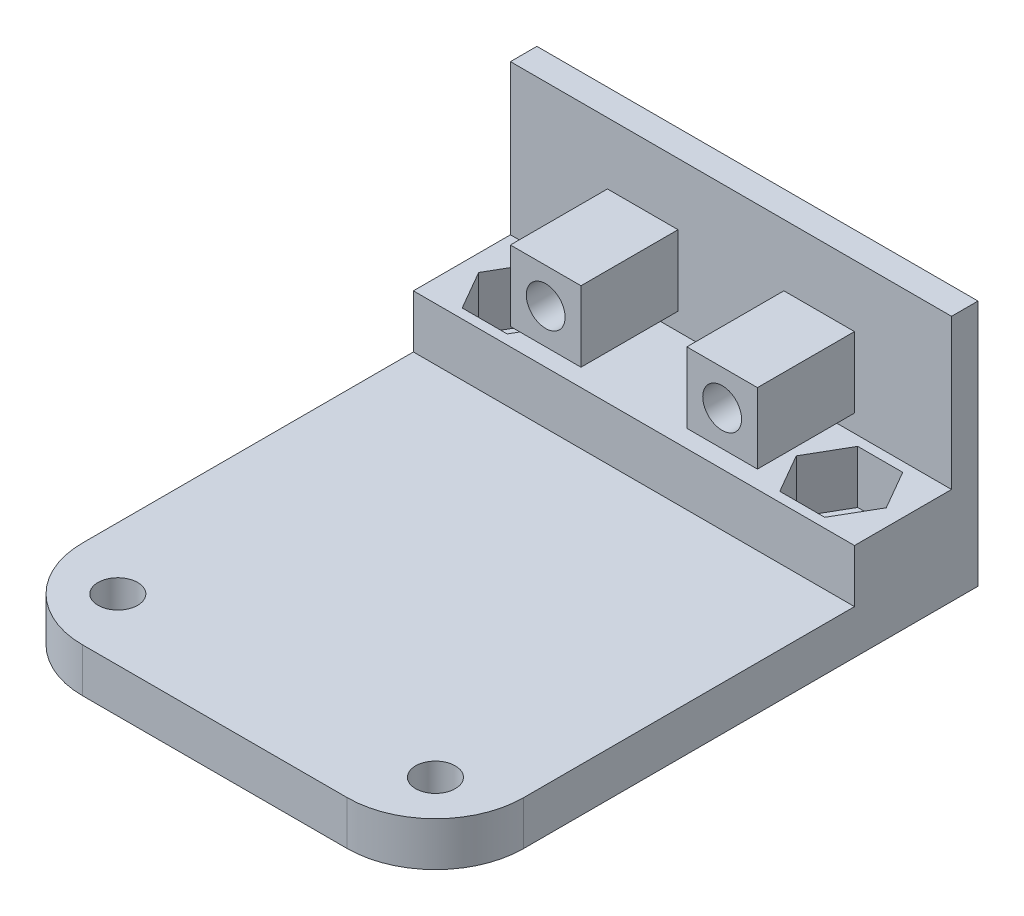
SolidWorks part; units mm, degrees
ref_plane "Front Plane" through (0, 0, 0) normal (0, 0, 1) x (1, 0, 0)
ref_plane "Top Plane" through (0, 0, 0) normal (0, 1, 0) x (1, 0, 0)
ref_plane "Right Plane" through (0, 0, 0) normal (1, 0, 0) x (0, 0, -1)
sketch "Sketch1" plane through (0, 0, 0) normal (0, 0, 1) x (1, 0, 0)
  line L1 (-25, 16.5) -> (25, 16.5)
  line L2 (-25, 16.5) -> (-25, -16.5)
  line L3 (-25, -16.5) -> (25, -16.5)
  line L4 (25, 16.5) -> (25, -16.5)
  line L5 (-25, 16.5) -> (25, -16.5) construction
  line L6 (-25, -16.5) -> (25, 16.5) construction
  point P0 (0, 0)
  dimension "D1" = 33
  dimension "D2" = 50
extrude "Boss-Extrude1" add sketch "Sketch1" along normal blind 3 contours L2 L3 L4 L1
sketch "Sketch2" plane through (0, 0, 3) normal (0, 0, 1) x (1, 0, 0)
  line L0 (25, 16.5) -> (25, -16.5) construction
  line L1 (-25, -16.5) -> (25, -16.5)
  line L2 (-25, -16.5) -> (-25, -11.5)
  line L3 (-25, -11.5) -> (25, -11.5)
  line L4 (25, -16.5) -> (25, -11.5)
  dimension "D1" = 5
extrude "Boss-Extrude2" add sketch "Sketch2" along normal blind 58.5
sketch "Sketch3" plane through (0, -11.5, 0) normal (0, 1, 0) x (1, 0, 0)
  line L0 (-25, -51.5) -> (-25, -61.5)
  line L1 (-25, -61.5) -> (-15, -61.5)
  line L2 (15, -61.5) -> (25, -61.5)
  line L3 (25, -61.5) -> (25, -51.5)
  arc A1 (15, -61.5) -> (25, -51.5) centre (15, -51.5) ccw construction
  arc A2 (15, -61.5) -> (25, -51.5) centre (15, -51.5) ccw
  arc A3 (-25, -51.5) -> (-15, -61.5) centre (-15, -51.5) ccw construction
  arc A4 (-25, -51.5) -> (-15, -61.5) centre (-15, -51.5) ccw
  circle A5 centre (-18, -54.5) radius 2.2479 construction
  circle A6 centre (-18, -54.5) radius 2.2479
  circle A7 centre (18, -54.5) radius 2.2479 construction
  circle A8 centre (18, -54.5) radius 2.2479
  circle A9 centre (-18, -8.5) radius 2.2479 construction
  circle A10 centre (-18, -8.5) radius 2.2479
  circle A11 centre (18, -8.5) radius 2.2479 construction
  circle A12 centre (18, -8.5) radius 2.2479
extrude "Cut-Extrude1" cut sketch "Sketch3" against normal up to surface (5 mm away) up to face at (0, -16.5, 30.75)
sketch "Sketch4" plane through (0, 0, 3) normal (0, 0, 1) x (1, 0, 0)
  line L5 (-14.0006, 4.5) -> (-6.0006, 4.5)
  line L6 (-14.0006, 4.5) -> (-14.0006, -3.5)
  line L7 (-14.0006, -3.5) -> (-6.0006, -3.5)
  line L8 (-6.0006, 4.5) -> (-6.0006, -3.5)
  line L9 (-14.0006, 4.5) -> (-6.0006, -3.5) construction
  line L10 (-14.0006, -3.5) -> (-6.0006, 4.5) construction
  line L11 (5.9994, 4.5) -> (13.9994, 4.5)
  line L12 (5.9994, 4.5) -> (5.9994, -3.5)
  line L13 (5.9994, -3.5) -> (13.9994, -3.5)
  line L14 (13.9994, 4.5) -> (13.9994, -3.5)
  line L15 (5.9994, 4.5) -> (13.9994, -3.5) construction
  line L16 (5.9994, -3.5) -> (13.9994, 4.5) construction
  circle A0 centre (-10.0006, 0.5) radius 2.2 construction
  circle A1 centre (-10.0006, 0.5) radius 2.2
  circle A2 centre (9.9994, 0.5) radius 2.2 construction
  circle A3 centre (9.9994, 0.5) radius 2.2
  dimension "D1" = 8
extrude "Boss-Extrude3" add sketch "Sketch4" along normal blind 11
sketch "Sketch5" plane through (0, 0, 14) normal (0, 0, 1) x (1, 0, 0)
  circle A0 centre (9.9994, 0.5) radius 2.2 construction
  circle A1 centre (9.9994, 0.5) radius 2.2
  circle A2 centre (-10.0006, 0.5) radius 2.2 construction
  circle A3 centre (-10.0006, 0.5) radius 2.2
extrude "Cut-Extrude2" cut sketch "Sketch5" against normal up to surface (14 mm away) up to face at (0, 0, 0)
sketch "Sketch6" plane through (0, 0, 3) normal (0, 0, 1) x (1, 0, 0)
  line L0 (25, 16.5) -> (25, -11.5) construction
  line L1 (-25, 16.5) -> (25, 16.5)
  line L2 (-25, 16.5) -> (-25, 11.5)
  line L3 (-25, 11.5) -> (25, 11.5)
  line L4 (25, 16.5) -> (25, 11.5)
  dimension "D1" = 5
extrude "Cut-Extrude3" cut sketch "Sketch6" against normal up to surface (3 mm away) up to face at (7.7994, 0.5, 0)
sketch "Sketch7" plane through (0, -11.5, 0) normal (0, 1, 0) x (1, 0, 0)
  line L0 (25, -51.5) -> (25, -3) construction
  line L1 (-25, -3) -> (25, -3)
  line L2 (-25, -3) -> (-25, -14)
  line L3 (-25, -14) -> (25, -14)
  line L4 (25, -3) -> (25, -14)
  dimension "D1" = 11
extrude "Boss-Extrude4" add sketch "Sketch7" along normal blind 6
sketch "Sketch8" plane through (0, -5.5, 0) normal (0, 1, 0) x (1, 0, 0)
  line L0 (25, -3) -> (-25, -3) construction
  line L1 (-15.45, -4.0833) -> (-20.55, -4.0833)
  line L2 (-20.55, -4.0833) -> (-23.1, -8.5)
  line L3 (-23.1, -8.5) -> (-20.55, -12.9167)
  line L4 (-20.55, -12.9167) -> (-15.45, -12.9167)
  line L5 (-15.45, -12.9167) -> (-12.9, -8.5)
  line L6 (-12.9, -8.5) -> (-15.45, -4.0833)
  line L8 (0, -15.4) -> (0, 15.4) construction
  line L9 (12.9, -8.5) -> (15.45, -4.0833)
  line L10 (15.45, -12.9167) -> (12.9, -8.5)
  line L11 (20.55, -12.9167) -> (15.45, -12.9167)
  line L12 (23.1, -8.5) -> (20.55, -12.9167)
  line L13 (20.55, -4.0833) -> (23.1, -8.5)
  line L14 (15.45, -4.0833) -> (20.55, -4.0833)
  circle A0 centre (-18, -8.5) radius 2.2479 construction
  circle A1 centre (-18, -8.5) radius 2.2479 construction
  circle A2 centre (-18, -8.5) radius 4.4167 construction
  circle A3 centre (18, -8.5) radius 4.4167 construction
  circle A4 centre (18, -8.5) radius 2.2479 construction
  dimension "D1" = 5.1
extrude "Cut-Extrude4" cut sketch "Sketch8" against normal blind 6
